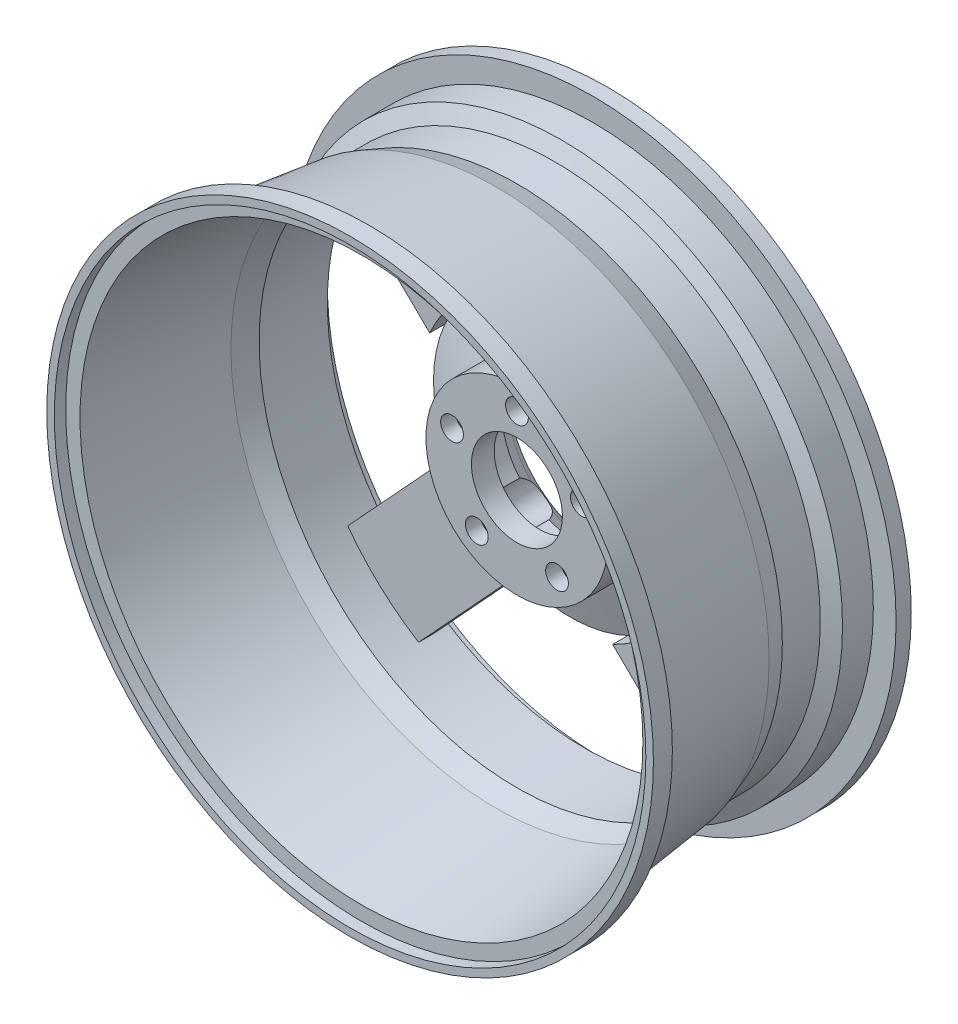
SolidWorks part; units mm, degrees
material "4032-T6"
ref_plane "Front Plane" through (0, 0, 0) normal (0, 0, 1) x (1, 0, 0)
ref_plane "Top Plane" through (0, 0, 0) normal (0, 1, 0) x (1, 0, 0)
ref_plane "Right Plane" through (0, 0, 0) normal (1, 0, 0) x (0, 0, -1)
sketch "Sketch1" plane through (0, 0, 0) normal (1, 0, 0) x (0, 0, -1)
  line L0 (0, 0) -> (0, 241.3) construction
  line L1 (31.75, 38.1) -> (50.8, 38.1)
  line L2 (105.6083, 95.0956) -> (76.2, 114.3)
  line L3 (0, 0) -> (171.9647, 0) construction
  line L4 (31.75, 38.1) -> (31.75, 76.2)
  line L5 (31.75, 76.2) -> (63.5, 76.2)
  line L6 (82.55, 63.5) -> (93.1478, 69.6187)
  line L7 (76.2, 215.9) -> (31.75, 215.9)
  line L8 (31.75, 215.9) -> (14.4879, 222.1829)
  line L9 (14.4879, 222.1829) -> (-98.425, 235.663)
  line L10 (-98.425, 235.663) -> (-98.425, 247.65)
  line L11 (-98.425, 247.65) -> (-107.95, 247.65)
  line L12 (-107.95, 247.65) -> (-107.95, 254)
  line L13 (-107.95, 254) -> (-92.075, 254)
  line L14 (-92.075, 254) -> (-92.075, 241.3)
  line L15 (-92.075, 241.3) -> (14.3035, 228.6)
  line L16 (14.3035, 228.6) -> (31.75, 222.25)
  line L17 (31.75, 222.25) -> (63.5, 222.25)
  line L18 (63.5, 222.25) -> (69.4221, 234.95)
  line L19 (69.4221, 234.95) -> (95.25, 234.95)
  line L20 (95.25, 234.95) -> (95.25, 254)
  line L21 (95.25, 254) -> (107.95, 254)
  line L22 (107.95, 254) -> (107.95, 247.65)
  line L23 (107.95, 247.65) -> (101.6, 247.65)
  line L24 (101.6, 247.65) -> (101.6, 228.6)
  line L25 (101.6, 228.6) -> (88.9, 228.6)
  line L26 (63.5, 76.2) -> (76.2, 114.3)
  line L27 (76.2, 215.9) -> (88.9, 215.9)
  line L28 (82.55, 63.5) -> (50.8, 63.5)
  line L29 (88.9, 215.9) -> (88.9, 228.6)
  line L30 (50.8, 63.5) -> (50.8, 38.1)
  arc A0 (93.1478, 69.6187) -> (105.6083, 95.0956) centre (80.4478, 91.6157) ccw
  point P33 (107.95, 78.1647)
  dimension "D2" = 241.3
  dimension "D3" = 228.6
  dimension "D4" = 6.35
  dimension "D5" = 6.35
  dimension "D8" = 31.75
  dimension "D9" = 31.75
  dimension "D12" = 6.35
  dimension "D15" = 19.05
  dimension "D16" = 12.7
  dimension "D17" = 6.35
  dimension "D18" = 107.95
  dimension "D19" = 6.35
  dimension "D22" = 9.525
  dimension "D6" = 38.1
  dimension "D7" = 38.1
  dimension "D20" = 6.35
  dimension "D21" = 6.35
  dimension "D25" = 160
  dimension "D26" = 12.7
  dimension "D23" = 30
  dimension "D10" = 107.95
  dimension "D11" = 115
  dimension "D13" = 31.75
  dimension "D24" = 12.7
  dimension "D27" = 14.4879
  dimension "D29" = 101.6
  dimension "D31" = 6.35
  dimension "D33" = 19.05
  dimension "D14" = 63.5
  dimension "D30" = 31.75
revolve "Revolve1" add sketch "Sketch1" angle 360 about L3
sketch "Sketch2" plane through (0, 0, -50.8) normal (0, 0, -1) x (-1, 0, 0)
  circle A0 centre (0, 57.15) radius 9.525
  circle A1 centre (0, 0) radius 57.15 construction
  circle A2 centre (54.3529, 17.6603) radius 9.525
  circle A3 centre (33.5919, -46.2353) radius 9.525
  circle A4 centre (-33.5919, -46.2353) radius 9.525
  circle A5 centre (-54.3529, 17.6603) radius 9.525
  dimension "D1" = 19.05
  dimension "D2" = 114.3
  dimension "D3" = 5
extrude "Cut-Extrude1" cut sketch "Sketch2" against normal through all and the other way through all
sketch "Sketch3" plane through (0, 0, -50.8) normal (0, 0, -1) x (-1, 0, 0)
  circle A0 centre (0, 57.15) radius 15.875
  circle A1 centre (0, 0) radius 57.15 construction
  circle A2 centre (54.3536, 17.6613) radius 15.875
  circle A3 centre (33.5937, -46.2347) radius 15.875
  circle A4 centre (-33.5901, -46.2359) radius 15.875
  circle A5 centre (-54.3522, 17.6594) radius 15.875
  dimension "D2" = 31.75
  dimension "D1" = 5
extrude "Cut-Extrude2" cut sketch "Sketch3" along normal through all
chamfer "Chamfer1" distance 6.35 angle 45 5 edges at (63.8779, 17.6603, -50.8) (43.1169, -46.2353, -50.8) (-24.0669, -46.2353, -50.8) (-44.8279, 17.6603, -50.8) (9.525, 57.15, -50.8)
sketch "Skizze1" plane through (0, 0, -76.2) normal (0, 0, 1) x (1, 0, 0)
  line L0 (0, 215.9) -> (0, -215.9) construction
  line L1 (-215.9, 0) -> (215.9, 0) construction
  line L2 (155.7249, -149.5412) -> (-155.7249, 149.5412) construction
  line L3 (151.717, 153.6059) -> (-151.717, -153.6059) construction
  line L4 (177.4635, -122.9615) -> (-127.46, 174.2606) construction
  line L5 (123.6896, -176.9567) -> (-180.0623, 119.1234) construction
  line L6 (-114.0827, -183.2975) -> (173.4575, 128.5508) construction
  line L7 (-173.4575, -128.5508) -> (114.0827, 183.2975) construction
  line L8 (102.1718, 51.2388) -> (173.4575, 128.5508)
  line L9 (42.797, 105.9854) -> (114.0827, 183.2975)
  line L10 (-52.1297, 101.7201) -> (-127.46, 174.2606)
  line L11 (-104.7574, 45.7205) -> (-180.0623, 119.1234)
  line L12 (-102.1718, -51.2388) -> (-173.4575, -128.5508)
  line L13 (48.3848, -103.5539) -> (123.6896, -176.9567)
  line L14 (-114.0827, -183.2975) -> (-42.797, -105.9854)
  line L15 (102.7282, -50.1139) -> (177.4635, -122.9615)
  circle A0 centre (0, 0) radius 215.9 construction
  circle A1 centre (0, 0) radius 114.3 construction
  circle A2 centre (0, 0) radius 215.9
  circle A3 centre (0, 0) radius 114.3
  dimension "D1" = 76.2
  dimension "D2" = 424.18
  dimension "D3" = 424.18
  dimension "D4" = 424.18
extrude "Aufsatz-Linear austragen1" add sketch "Skizze1" along normal blind 12.7 contours A3 L8 A2 L9 | A3 L10 A2 L11 | A3 L12 A2 L14 | A3 L13 A2 L15 region at (110.6547, 120.0092, -76.2) region at (115.4043, -115.741, -76.2) region at (-118.4807, 112.4629, -76.2) region at (-110.6547, -120.0092, -76.2)
